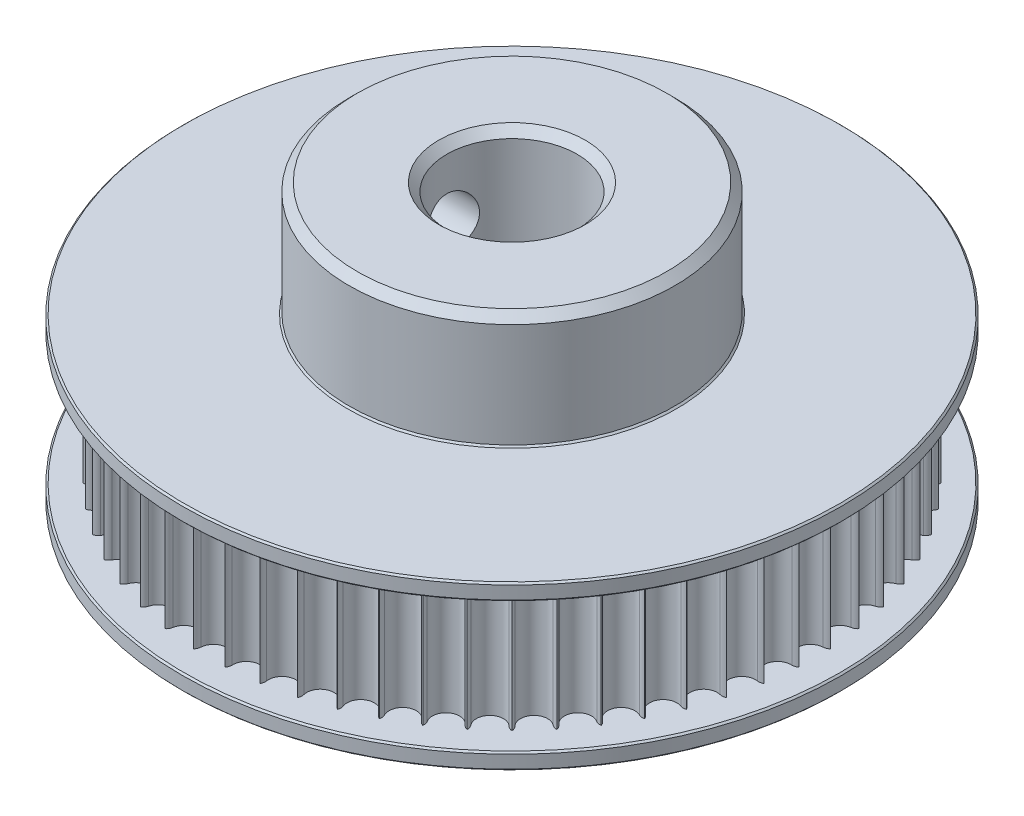
SolidWorks part; units mm, degrees
ref_plane "Front plan" through (0, 0, 0) normal (0, 0, 1) x (1, 0, 0)
ref_plane "Top plan" through (0, 0, 0) normal (0, 1, 0) x (1, 0, 0)
ref_plane "Right plan" through (0, 0, 0) normal (1, 0, 0) x (0, 0, -1)
sketch "Skica2" plane through (0, 0, 0) normal (0, 0, 1) x (1, 0, 0)
  line L0 (10, 9) -> (4, 9)
  line L1 (4, 9) -> (4, -9)
  line L2 (4, -9) -> (5, -9)
  line L3 (0, -9) -> (0, 9) construction
  line L4 (0, 9) -> (4, 9)
  line L5 (0, -9) -> (4, -9)
  line L6 (5, -9) -> (5, -8)
  line L7 (20.25, 1) -> (18.8, 1)
  line L8 (18.8, 1) -> (18.8, -7)
  line L9 (20.25, 1) -> (20.25, 2)
  line L12 (20.25, -8) -> (5, -8)
  line L13 (20.25, 2) -> (10, 2)
  line L14 (20.25, -8) -> (20.25, -7)
  line L15 (18.8, -7) -> (20.25, -7)
  line L16 (10, 2) -> (10, 9)
  point P2 (6.9432, -7.5)
  point P6 (12.625, -8)
  point P7 (0, 0)
  point P17 (7.5179, -7.5)
  dimension "D2" = 1
  dimension "D6" = 40.5
  dimension "D3" = 37.6
  dimension "D1" = 8
  dimension "D8" = 18
  dimension "D4" = 1
  dimension "D7" = 20
  dimension "D9" = 7
  dimension "D5" = 1
revolve "Revolute" add sketch "Skica2" angle 360 about L3 region at (10.5329, -1.1872, 0)
sketch "Sketch2" plane through (0, 1, 0) normal (0, -1, 0) x (1, 0, 0)
  line L0 (0, 0) -> (0, 18.3305) construction
  line L1 (0, 0) -> (6.3393, 17.699) construction
  line L3 (0, 0) -> (-2.1448, 18.6773) construction
  circle A1 centre (0, 0) radius 17.4945 construction
  circle A2 centre (0, 0) radius 18.3 construction
  arc A3 (-0.8345, 18.281) -> (0.8345, 18.281) centre (0, 18.3305) ccw
  arc A7 (-1.3701, 18.75) -> (-2.1448, 18.6773) centre (0, 0) ccw
  arc A8 (0, 20.2554) -> (2.1448, 18.6773) centre (0.5756, 18.7912) cw
  circle A9 centre (0, 0) radius 18.8 construction
  arc A10 (1.3701, 18.75) -> (2.1448, 18.6773) centre (0, 0) cw
  arc A11 (1.3701, 18.75) -> (0.8345, 18.281) centre (1.3336, 18.2513) ccw
  arc A12 (0, 20.2554) -> (-2.1448, 18.6773) centre (-0.5756, 18.7912) ccw
  arc A13 (-1.3701, 18.75) -> (-0.8345, 18.281) centre (-1.3336, 18.2513) cw
  point P0 (0.8326, 11.926)
  dimension "D2" = 1
  dimension "D4" = 0.836
  dimension "D6" = 37.6
  dimension "D3" = 1.5733
  dimension "D1" = 0.5
extrude "Cut-Extrude3" cut sketch "Sketch2" along normal up to surface (8 mm away) up to face at (20.25, -7, 0)
pattern_circular "CirPattern1" count 60 over 360 about axis through (0, -9, 0) along (0, -1, 0) of "Cut-Extrude3"
sketch "Sketch3" plane through (0, 0, 0) normal (1, 0, 0) x (0, 0, -1)
  line L0 (0, 9) -> (0, 0.5) construction
  line L1 (4, 9) -> (-4, 9) construction
  circle A0 centre (0, 4.75) radius 1.65
  dimension "D1" = 3.3
extrude "Cut-Extrude2" cut sketch "Sketch3" against normal up to next
chamfer "Chamfer1" distance 1 angle 45 1 edges at (5, -8, 0)
chamfer "Chamfer2" distance 0.5 angle 45 2 edges at (10, 9, 0) (4, 9, 0)
chamfer "Chamfer3" distance 0.1 angle 45 5 edges at (20.25, -8, 0) (20.25, -7, 0) (20.25, 1, 0) (20.25, 2, 0) (10, 2, 0)
equation "\"`\"=2"
equation "\"D6@Sketch2\"= \"D3@Skica2\""
